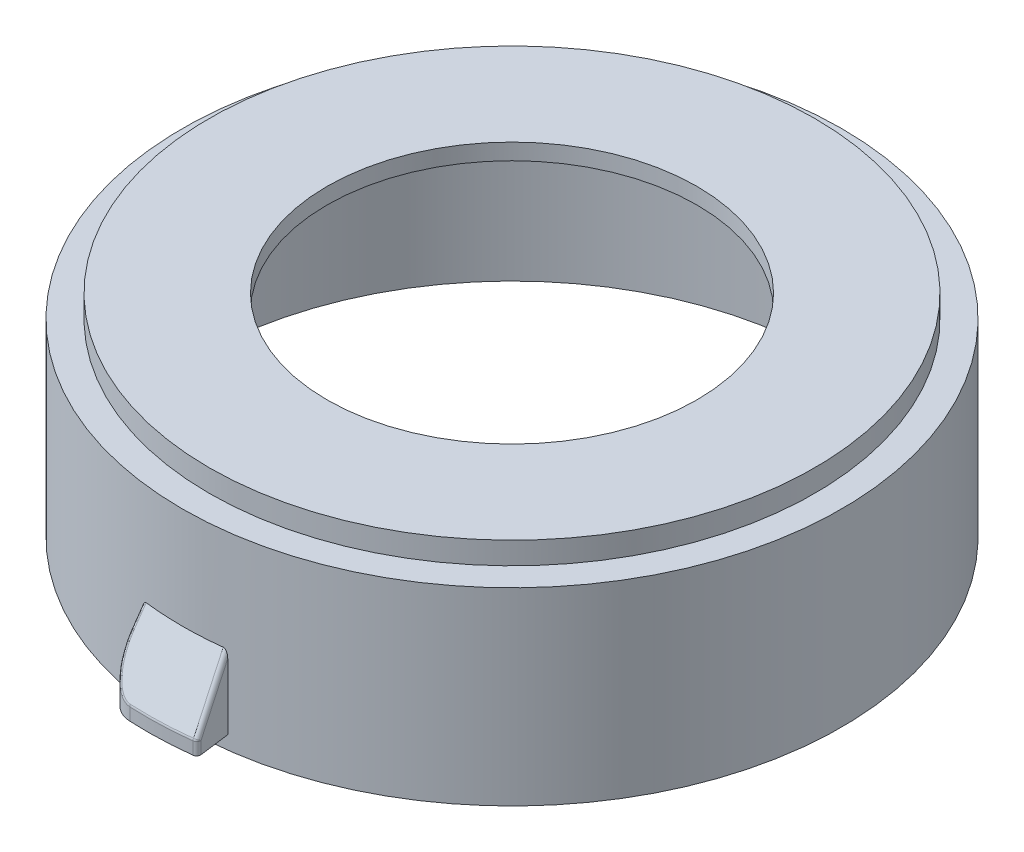
SolidWorks part; units mm, degrees
ref_plane "Front Plane" through (0, 0, 0) normal (0, 0, 1) x (1, 0, 0)
ref_plane "Top Plane" through (0, 0, 0) normal (0, 1, 0) x (1, 0, 0)
ref_plane "Right Plane" through (0, 0, 0) normal (1, 0, 0) x (0, 0, -1)
sketch "Sketch1" plane through (0, 0, 0) normal (0, 1, 0) x (1, 0, 0)
  circle A0 centre (0, 0) radius 24.5
  dimension "D1" = 49
extrude "Boss-Extrude1" add sketch "Sketch1" along normal blind 15.7
sketch "Sketch2" plane through (0, 15.7, 0) normal (0, 1, 0) x (1, 0, 0)
  circle A0 centre (0, 0) radius 22.5
  circle A1 centre (0, 0) radius 24.5 construction
  circle A2 centre (0, 0) radius 24.5
  dimension "D1" = 45
extrude "Cut-Extrude1" cut sketch "Sketch2" against normal blind 1.65
sketch "Sketch3" plane through (0, 15.7, 0) normal (0, 1, 0) x (1, 0, 0)
  circle A0 centre (0, 0) radius 13.75
  dimension "D1" = 27.5
shell "Shell1" thickness 1.2 removed face at (0, 0, 24.5)
extrude "Cut-Extrude2" cut sketch "Sketch3" against normal up to surface (1.2 mm away) up to face at (0, 14.5, 21.3)
sketch "Sketch4" plane through (0, 0, 0) normal (1, 0, 0) x (0, 0, -1)
  line L0 (-24.5, 6.5) -> (-24.5, 1)
  line L1 (-24.5, 14.05) -> (-24.5, 0) construction
  line L2 (-24.5, 14.05) -> (-24.5, 0) construction
  line L3 (-24.5, 1) -> (-27.1, 1)
  line L4 (-27.1, 1) -> (-27.1, 2)
  line L5 (-27.1, 2) -> (-24.5, 6.5)
  dimension "D1" = 2.6
  dimension "D2" = 1
  dimension "D3" = 5.5
  dimension "D4" = 1
ref_plane "Plane1" through (0, 1, 24.5) normal (0, -1, 0) x (-1, 0, 0)
sketch "Sketch5" plane through (0, 1, 24.5) normal (0, -1, 0) x (-1, 0, 0)
  line L0 (0, 0) -> (0, -8.4757) construction
  line L1 (0, 0) -> (0, -2.6) construction
  line L2 (0, -2.6) -> (-6.262, -2.6) construction
  line L3 (-3.5, -2.373) -> (-3.5, -2.6) construction
  line L4 (3.5, -2.373) -> (3.5, -2.6) construction
  circle A2 centre (0, 24.5) radius 27.1
  arc A3 (-3.5, -2.373) -> (3.5, -2.373) centre (0, 24.5) ccw
  point P15 (0, -2.6)
  dimension "D2" = 3.5
  dimension "D3" = 3.5
  dimension "D1" = 2.6
sweep "Sweep1" add profiles "Sketch4" path "Sketch5"
fillet "Fillet2" radius 2 1 edges at (-3.5, 1.5, 26.873)
fillet "Fillet3" radius 0.3 5 edges at (-3.1978, 6.0498, 24.5527) (1.0805, 2, 27.0784) (3.5, 1.5, 26.873) (3.3321, 4.25, 25.5839) (-2.2759, 2.3787, 26.7847)
